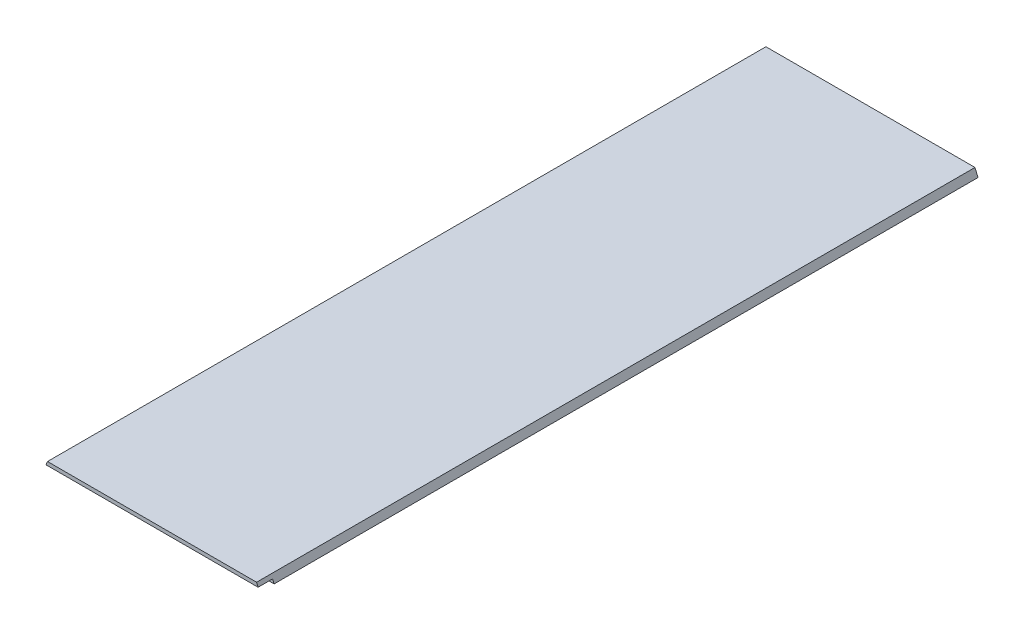
SolidWorks part; units mm, degrees
ref_plane "Front Plane" through (0, 0, 0) normal (0, 0, 1) x (1, 0, 0)
ref_plane "Top Plane" through (0, 0, 0) normal (0, 1, 0) x (1, 0, 0)
ref_plane "Right Plane" through (0, 0, 0) normal (1, 0, 0) x (0, 0, -1)
sketch "Sketch1" plane through (0, 0, 0) normal (0, 0, 1) x (1, 0, 0)
  line L0 (0, 0) -> (2.6303, 6.35)
  line L1 (2.6303, 6.35) -> (185.5837, 6.35)
  line L2 (185.5837, 6.35) -> (188.214, 0)
  line L3 (188.214, 0) -> (0, 0)
  dimension "D1" = 6.35
  dimension "D2" = 67.5
  dimension "D3" = 67.5
  dimension "D4" = 188.214
extrude "Boss-Extrude1" add sketch "Sketch1" along normal blind 628.65
sketch "Sketch2" plane through (0, 0, 0) normal (0, -1, 0) x (1, 0, 0)
  line L0 (188.214, 628.65) -> (188.214, 0) construction
  line L1 (0, 628.65) -> (188.214, 628.65)
  line L2 (0, 628.65) -> (0, 615.95)
  line L3 (0, 615.95) -> (188.214, 615.95)
  line L4 (188.214, 628.65) -> (188.214, 615.95)
  dimension "D1" = 12.7
extrude "Cut-Extrude1" cut sketch "Sketch2" against normal blind 3.175
